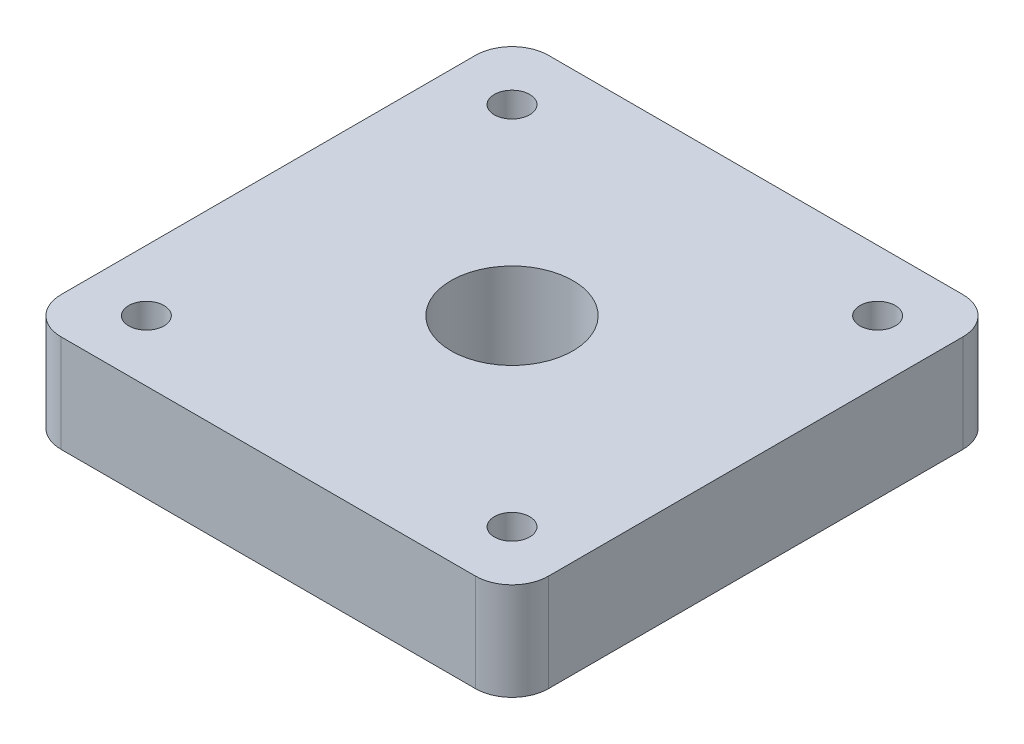
SolidWorks part; units mm, degrees
ref_plane "Front Plane" through (0, 0, 0) normal (0, 0, 1) x (1, 0, 0)
ref_plane "Top Plane" through (0, 0, 0) normal (0, 1, 0) x (1, 0, 0)
ref_plane "Right Plane" through (0, 0, 0) normal (1, 0, 0) x (0, 0, -1)
sketch "Sketch1" plane through (0, 0, 0) normal (0, 1, 0) x (1, 0, 0)
  line L1 (0, 0.1114) -> (40, 0.1114)
  line L2 (0, 0.1114) -> (0, -39.8886)
  line L3 (0, -39.8886) -> (40, -39.8886)
  line L4 (40, 0.1114) -> (40, -39.8886)
  circle A0 centre (20, -19.8886) radius 5
  dimension "D5" = 10
  dimension "D1" = 40
  dimension "D2" = 40
  dimension "D3" = 20
  dimension "D4" = 20
extrude "Boss-Extrude1" add sketch "Sketch1" along normal blind 8
sketch "Sketch12" plane through (0, 8, 0) normal (0, 1, 0) x (1, 0, 0)
  line L0 (40, 0.1114) -> (0, 0.1114) construction
  line L1 (0, 0.1114) -> (0, -39.8886) construction
  line L2 (40, -39.8886) -> (40, 0.1114) construction
  line L3 (0, -39.8886) -> (40, -39.8886) construction
  circle A0 centre (5, -4.8886) radius 1.45
  circle A1 centre (35, -4.8886) radius 1.45
  circle A2 centre (35, -34.8886) radius 1.45
  circle A3 centre (5, -34.8886) radius 1.45
  point P16 (0, 0)
  point P18 (0, -35.4616)
  dimension "D1" = 2.9
  dimension "D2" = 2.9
  dimension "D3" = 2.9
  dimension "D4" = 2.9
  dimension "D5" = 5
  dimension "D6" = 5
  dimension "D7" = 5
  dimension "D8" = 5
  dimension "D9" = 5
  dimension "D10" = 5
  dimension "D11" = 5
  dimension "D12" = 5
extrude "Cut-Extrude1" cut sketch "Sketch12" against normal through all
fillet "Fillet1" radius 3 4 edges at (40, 4, 39.8886) (40, 4, -0.1114) (0, 4, -0.1114) (0, 4, 39.8886)
